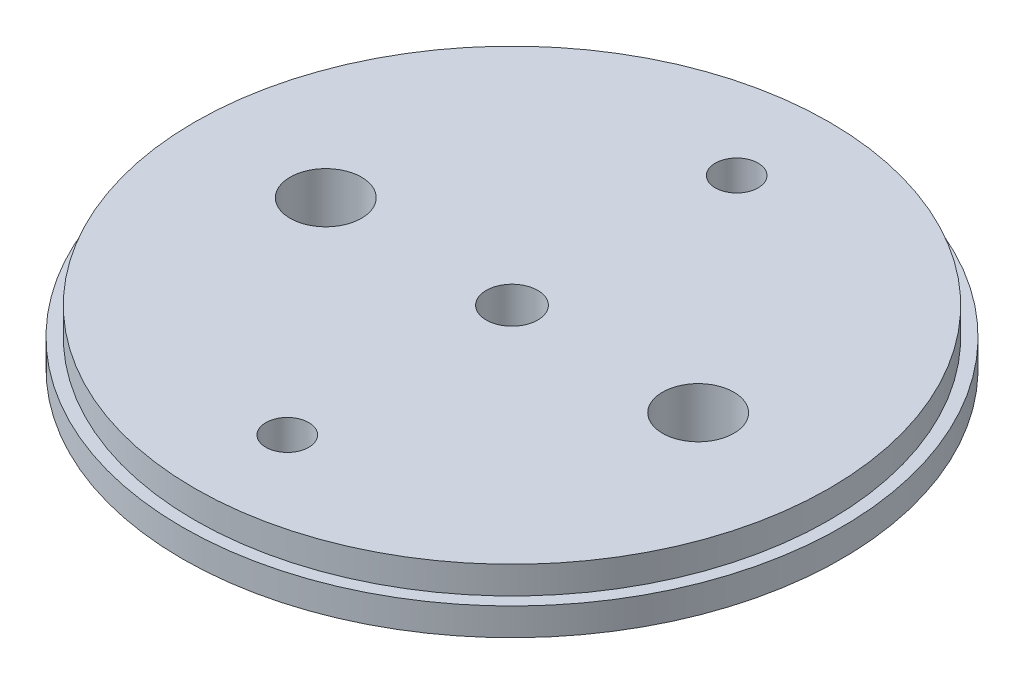
SolidWorks part; units mm, degrees
ref_plane "Front Plane" through (0, 0, 0) normal (0, 0, 1) x (1, 0, 0)
ref_plane "Top Plane" through (0, 0, 0) normal (0, 1, 0) x (1, 0, 0)
ref_plane "Right Plane" through (0, 0, 0) normal (1, 0, 0) x (0, 0, -1)
sketch "Sketch1" plane through (0, 0, 0) normal (0, 1, 0) x (1, 0, 0)
  circle A0 centre (0, 0) radius 73.3425
  circle A1 centre (0, 0) radius 76.1746
  dimension "D1" = 146.685
  dimension "D2" = 152.3492
extrude "Boss-Extrude1" add sketch "Sketch1" along normal blind 6.35 contours A0 | A1 A0 region at (0, 0, 0) region at (-74.0201, 0, 0)
extrude "Boss-Extrude2" add sketch "Sketch1<3>" along normal blind 12.7 contours A0 region at (0, 0, 0)
sketch "Sketch1<3>" plane through (0, 0, 0) normal (0, 1, 0) x (1, 0, 0) same geometry as "Sketch1"
sketch "Sketch3" plane through (0, 0, 0) normal (0, -1, 0) x (1, 0, 0)
  line L0 (43.0382, 0) -> (-43.0382, 0) construction
  line L1 (0, -51.9333) -> (0, 51.9333) construction
  circle A0 centre (0, 0) radius 5.9531
  circle A1 centre (-43.0382, 0) radius 8.25
  circle A2 centre (43.0382, 0) radius 8.25
  circle A3 centre (0, 51.9333) radius 4.9609
  circle A4 centre (0, -51.9333) radius 4.9609
  point P6 (0, 0)
  point P10 (43.0382, 0)
  point P11 (0, 51.9333)
  point P14 (0, 0)
  dimension "D1" = 11.9062
  dimension "D2" = 16.5001
  dimension "D3" = 9.9219
extrude "Cut-Extrude1" cut sketch "Sketch3" against normal through all
sketch "Sketch5" plane through (0, 12.7, 0) normal (0, 1, 0) x (1, 0, 0)
  line L1 (4.4764, 59.9313) -> (-4.6883, 59.8089)
  line L2 (-4.6883, 59.8089) -> (-9.1646, 51.811)
  line L3 (-9.1646, 51.811) -> (-4.4764, 43.9354)
  line L4 (-4.4764, 43.9354) -> (4.6883, 44.0577)
  line L5 (4.6883, 44.0577) -> (9.1646, 52.0557)
  line L6 (9.1646, 52.0557) -> (4.4764, 59.9313)
  line L7 (7.424, -57.3082) -> (8.3668, -48.1914)
  line L8 (8.3668, -48.1914) -> (0.9428, -42.8165)
  line L9 (0.9428, -42.8165) -> (-7.424, -46.5584)
  line L10 (-7.424, -46.5584) -> (-8.3668, -55.6752)
  line L11 (-8.3668, -55.6752) -> (-0.9428, -61.0501)
  line L12 (-0.9428, -61.0501) -> (7.424, -57.3082)
  circle A0 centre (0, 51.9333) radius 7.9375 construction
  circle A1 centre (0, -51.9333) radius 7.9375 construction
  dimension "D1" = 15.875
